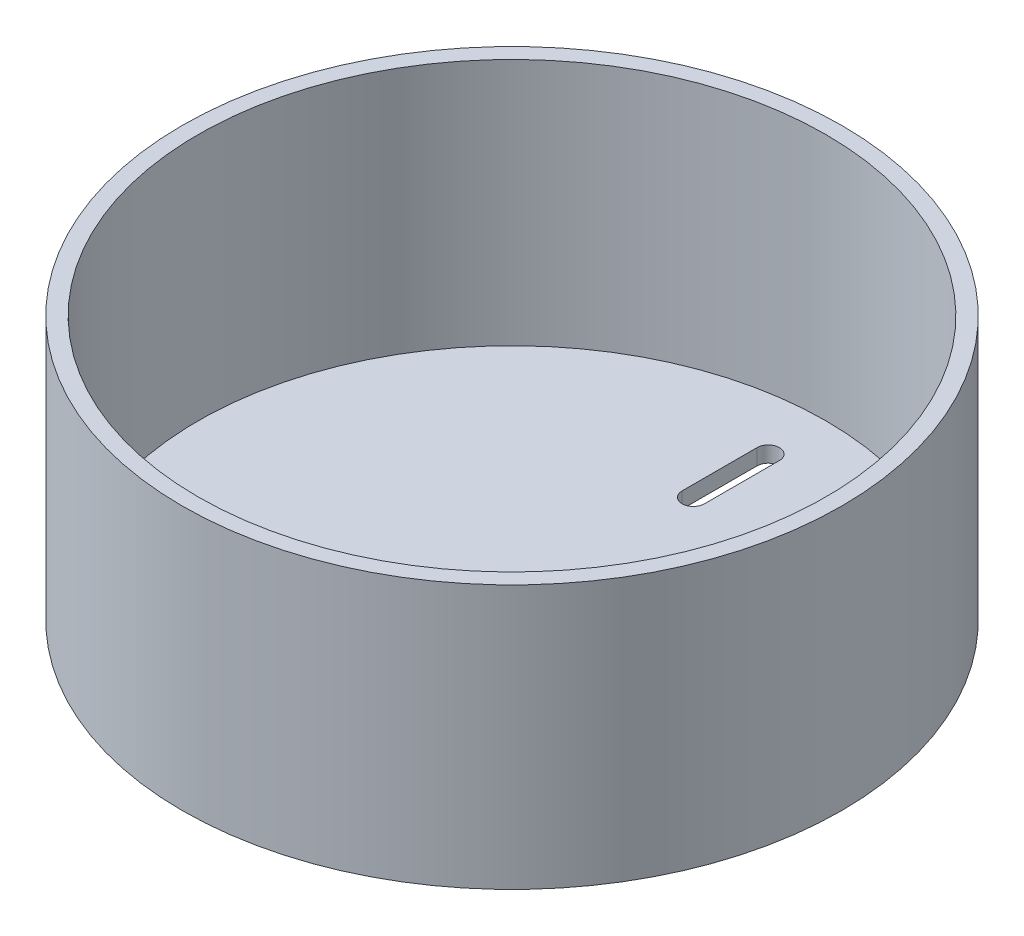
SolidWorks part; units mm, degrees
ref_plane "Front Plane" through (0, 0, 0) normal (0, 0, 1) x (1, 0, 0)
ref_plane "Top Plane" through (0, 0, 0) normal (0, 1, 0) x (1, 0, 0)
ref_plane "Right Plane" through (0, 0, 0) normal (1, 0, 0) x (0, 0, -1)
sketch "Sketch1" plane through (0, 0, 0) normal (0, 1, 0) x (1, 0, 0)
  circle A0 centre (0, 0) radius 62.5
  circle A1 centre (0, 0) radius 59.5
  dimension "D1" = 125
  dimension "D2" = 3
extrude "Boss-Extrude1" add sketch "Sketch1" along normal blind 3 contours A1 | A0 A1 region at (-60.7322, 0, 0) region at (0, 0, 0)
extrude "Boss-Extrude2" add sketch "Sketch1<3>" along normal blind 50
sketch "Sketch1<3>" plane through (0, 0, 0) normal (0, 1, 0) x (1, 0, 0) same geometry as "Sketch1"
sketch "Sketch2" plane through (0, 0, 0) normal (0, -1, 0) x (1, 0, 0)
  line L0 (0, -48.5732) -> (0, -34.3686) construction
  line L1 (-2.1225, -48.5732) -> (-2.1225, -34.3686)
  line L2 (2.1225, -48.5732) -> (2.1225, -34.3686)
  arc A0 (-2.1225, -48.5732) -> (2.1225, -48.5732) centre (0, -48.5732) ccw
  arc A1 (2.1225, -34.3686) -> (-2.1225, -34.3686) centre (0, -34.3686) ccw
  point P3 (0, -41.4709)
  dimension "D1" = 4.245
  dimension "D2" = 14.2046
extrude "Cut-Extrude1" cut sketch "Sketch2" against normal blind 50
